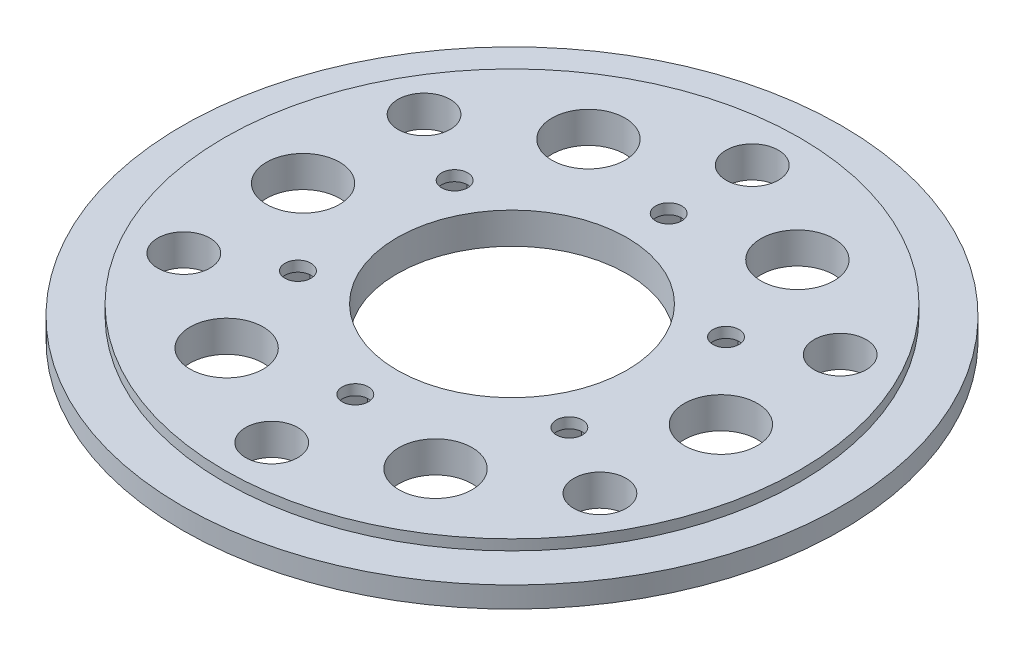
SolidWorks part; units mm, degrees
ref_plane "Front Plane" through (0, 0, 0) normal (0, 0, 1) x (1, 0, 0)
ref_plane "Top Plane" through (0, 0, 0) normal (0, 1, 0) x (1, 0, 0)
ref_plane "Right Plane" through (0, 0, 0) normal (1, 0, 0) x (0, 0, -1)
sketch "Sketch1" plane through (0, 0, 0) normal (0, 1, 0) x (1, 0, 0)
  circle A0 centre (0, 0) radius 27.55
  circle A1 centre (0, 0) radius 11
  circle A2 centre (0, 0) radius 31.55
  dimension "D1" = 55.1
  dimension "D3" = 22
  dimension "D2" = 4
extrude "Boss-Extrude1" add sketch "Sketch1" along normal blind 3 contours A0 A1 region at (-26.7708, 0, 0)
extrude "Boss-Extrude2" add sketch "Sketch1<3>" along normal blind 2 contours A2 A0 region at (-30.6576, 0, 0)
sketch "Sketch1<3>" plane through (0, 0, 0) normal (0, 1, 0) x (1, 0, 0) same geometry as "Sketch1"
hole_wizard "M3x0.5 Tapped Hole1" positions "Sketch2" profile "Sketch4" tap size "M3x0.5" standard "ANSI Metric" end condition through all
sketch "Sketch2" plane through (0, 3, 0) normal (0, 1, 0) x (1, 0, 0)
  line L0 (0, 0) -> (0, 15) construction
  point P0 (0, 15)
  dimension "D1" = 15
sketch "Sketch4" plane through (0, 3, -15) normal (1, 0, 0) x (0, 0, 1)
  line L0 (0, 0) -> (0, 3)
  line L1 (0, 3) -> (1.25, 3)
  line L2 (1.25, 3) -> (1.25, 0)
  line L5 (1.25, 0) -> (0, 0)
  line L11 (0, -6.35) -> (0, 107.95) construction
  dimension "Thru Tap Drill Dia." = 2.5
  dimension "Thru Tap Drill Depth" = 3
sketch "Sketch6" plane through (0, 3, 0) normal (0, 1, 0) x (1, 0, 0)
  line L0 (0, 0) -> (20, 0) construction
  line L1 (0, 0) -> (0, 23) construction
  circle A0 centre (20, 0) radius 3.5
  circle A1 centre (0, 23) radius 2.5
  dimension "D2" = 7
  dimension "D4" = 5
  dimension "D1" = 20
  dimension "D3" = 23
extrude "Cut-Extrude1" cut sketch "Sketch6" against normal through all
pattern_circular "CirPattern1" count 6 over 360 about axis through (0, 3, 0) along (0, -1, 0) of "M3x0.5 Tapped Hole1", "Cut-Extrude1" reverse direction yes
sketch "Sketch7" plane through (0, 0, 0) normal (0, -1, 0) x (1, 0, 0)
  line L0 (0, 0) -> (0, 12.25) construction
  line L1 (1.5877, 12.25) -> (3.1754, 15)
  line L2 (3.1754, 15) -> (1.5877, 17.75)
  line L3 (1.5877, 17.75) -> (-1.5877, 17.75)
  line L4 (-1.5877, 17.75) -> (-3.1754, 15)
  line L5 (-3.1754, 15) -> (-1.5877, 12.25)
  line L6 (-1.5877, 12.25) -> (1.5877, 12.25)
  circle A0 centre (0, 15) radius 2.75 construction
  dimension "D1" = 5.5
extrude "Cut-Extrude2" cut sketch "Sketch7" against normal blind 2
pattern_circular "CirPattern2" count 6 over 360 about axis through (0, 3, 0) along (0, -1, 0) of "Cut-Extrude2" reverse direction yes
equation "\"Ratio\"= 15"
equation "\"Hull Diameter\"= 92"
equation "\"Fixed Ring Diameter\"= 76"
equation "\"Fixed Pin Diameter\"= 6"
equation "\"Output Ring Diameter\"= 40"
equation "\"Output Pin Diameter\"= 6"
equation "\"Disk Bearing Inner Diameter\"= 9"
equation "\"Disk Bearing Outer Diameter\"= 17"
equation "\"Disk Bearing Height\"= 5"
equation "\"Shaft Bearing Inner Diameter\"= 15"
equation "\"Shaft Bearing Outer Diameter\"= 21"
equation "\"Shaft Bearing Height\"= 4"
equation "\"Eccentricity\"= 1.5"
equation "\"Disk Height\"= 8"
equation "\"Disk Spacing\"= 5"
equation "\"Hull Height\"= 40"
equation "\"Shaft End Bearing Inner Diameter\"= 12"
equation "\"Shaft End Bearing Outer Diameter\"= 18"
equation "\"Shaft End Bearing Height\"= 4"
equation "\"Output Bearing Inner Diameter\"= 55"
equation "\"Output Bearing Outer Diameter\"= 72"
equation "\"Outer Bearing Height\"= 9"
equation "\"D1@Sketch1\"=\"Output Bearing Inner Diameter\"+0.1"
